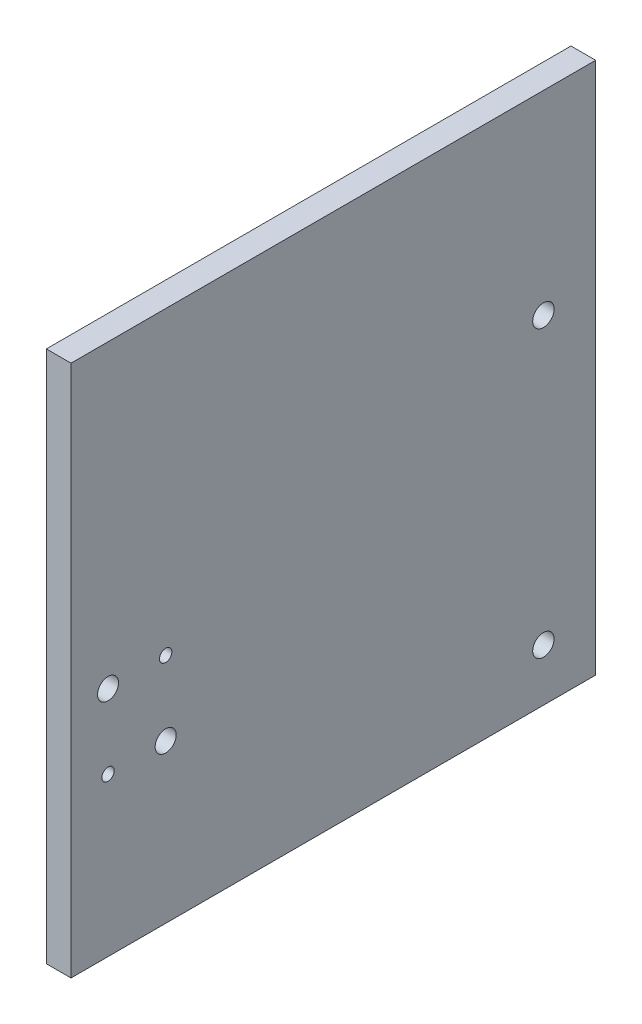
SolidWorks part; units mm, degrees
ref_plane "Front Plane" through (0, 0, 0) normal (1, 0, 0) x (0, 1, 0)
ref_plane "Top Plane" through (0, 0, 0) normal (0, 0, 1) x (0, 1, 0)
ref_plane "Right Plane" through (0, 0, 0) normal (0, 1, 0) x (-1, 0, 0)
sketch "Sketch1" plane through (0, 0, 0) normal (1, 0, 0) x (0, 1, 0)
  line L0 (0, 25) -> (0, -25) construction
  line L1 (-47.4, -25) -> (47.4, -25) construction
  line L2 (-47.4, -25) -> (-47.4, 25) construction
  line L3 (-47.4, 25) -> (47.4, 25) construction
  line L4 (47.4, -25) -> (47.4, 25) construction
  line L5 (-47.4, -25) -> (47.4, 25) construction
  line L6 (-47.4, 25) -> (47.4, -25) construction
  line L7 (-47.4, 16) -> (47.4, 16)
  line L8 (-9, -7) -> (9, -7) construction
  line L9 (-9, -7) -> (-9, 7) construction
  line L10 (-9, 7) -> (9, 7) construction
  line L11 (9, -7) -> (9, 7) construction
  line L12 (-9, -7) -> (9, 7) construction
  line L13 (-9, 7) -> (9, -7) construction
  line L14 (-34.7, -15) -> (34.7, -15) construction
  line L15 (-34.7, -15) -> (-34.7, 15) construction
  line L16 (-34.7, 15) -> (34.7, 15) construction
  line L17 (34.7, -15) -> (34.7, 15) construction
  line L18 (-34.7, -15) -> (34.7, 15) construction
  line L19 (-34.7, 15) -> (34.7, -15) construction
  line L20 (-47.4, -25) -> (47.4, -25) construction
  line L21 (-47.4, -25) -> (-47.4, -111.5)
  line L22 (-47.4, -111.5) -> (47.4, -111.5)
  line L23 (47.4, -25) -> (47.4, -111.5) construction
  line L24 (-47.4, -111.5) -> (-34.7, -111.5) construction
  line L25 (-47.4, -111.5) -> (-47.4, -98.8) construction
  line L26 (-47.4, -98.8) -> (-34.7, -98.8) construction
  line L27 (-34.7, -111.5) -> (-34.7, -98.8) construction
  line L28 (47.4, -111.5) -> (34.7, -111.5) construction
  line L29 (47.4, -111.5) -> (47.4, -98.8) construction
  line L30 (47.4, -98.8) -> (34.7, -98.8) construction
  line L31 (34.7, -111.5) -> (34.7, -98.8) construction
  line L32 (47.4, -25) -> (47.4, 16) construction
  line L33 (-47.4, 16) -> (-47.4, -25)
  line L35 (47.4, 16) -> (82, 16)
  line L36 (47.4, 16) -> (47.4, -111.5) construction
  line L37 (47.4, -111.5) -> (82, -111.5)
  line L38 (82, 16) -> (82, -111.5)
  circle A0 centre (-9, 7) radius 1.5
  circle A1 centre (-9, -7) radius 2.555
  circle A2 centre (9, -7) radius 1.5
  circle A3 centre (9, 7) radius 2.555
  circle A4 centre (-34.7, 15) radius 2.555 construction
  circle A5 centre (-34.7, -15) radius 2.555 construction
  circle A6 centre (34.7, 15) radius 2.555 construction
  circle A7 centre (34.7, -15) radius 2.555 construction
  circle A8 centre (-34.7, -98.8) radius 2.6
  circle A9 centre (34.7, -98.8) radius 2.6
  point P0 (0, 0)
  point P8 (0, 0)
  point P17 (0, 0)
  dimension "D5" = 5.11
  dimension "D6" = 3
  dimension "D9" = 5.11
  dimension "D10" = 5.11
  dimension "D11" = 5.11
  dimension "D12" = 3
  dimension "D13" = 3
  dimension "D17" = 5.2
  dimension "D18" = 9
  dimension "D1" = 14
  dimension "D2" = 18
  dimension "D3" = 94.8
  dimension "D4" = 50
  dimension "D7" = 12.7
  dimension "D8" = 30
  dimension "D14" = 86.5
  dimension "D15" = 12.7
  dimension "D16" = 12.7
  dimension "D19" = 34.6
extrude "Boss-Extrude1" add sketch "Sketch1" along normal blind 6
